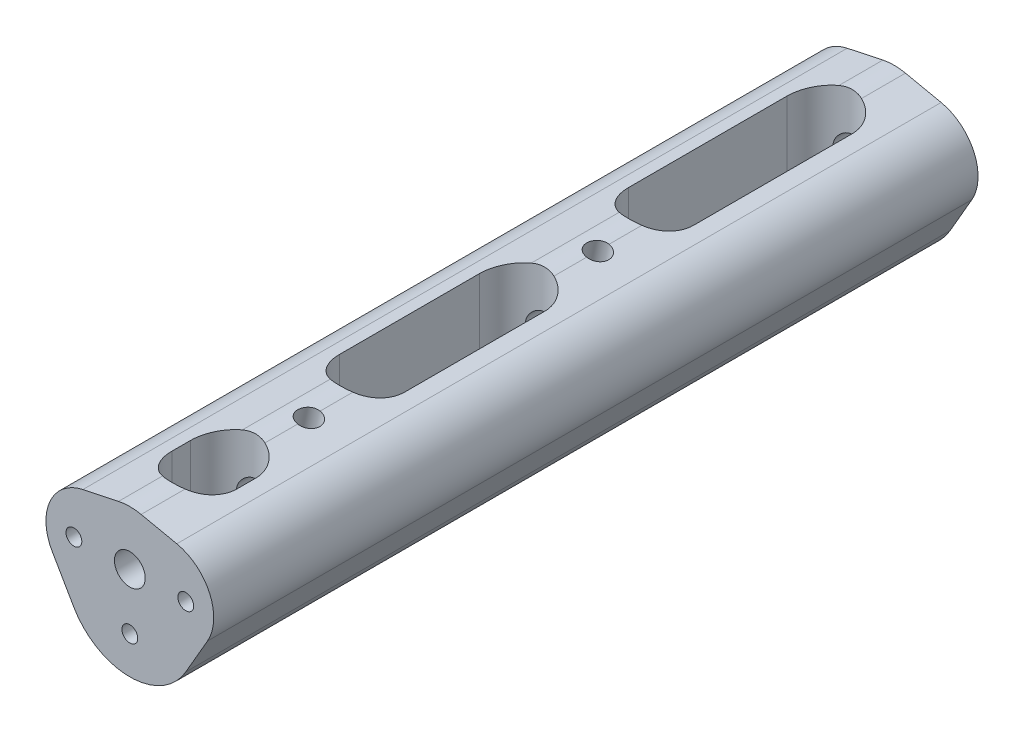
SolidWorks part; units mm, degrees
other "Pillar2"
material "Nylon 101"
ref_plane "Front" through (0, 0, 0) normal (0, 0, 1) x (1, 0, 0)
ref_plane "Top" through (0, 0, 0) normal (0, 1, 0) x (1, 0, 0)
ref_plane "Right" through (0, 0, 0) normal (1, 0, 0) x (0, 0, -1)
ref_axis "Axis" through (0, 0, -80.9) along (0, 0, 1)
sketch "BodySke" plane through (0, 0, 0) normal (0, 0, 1) x (1, 0, 0)
  line L0 (-2, 0) -> (2, 0) construction
  line L1 (-2, 2.5) -> (2, 2.5) construction
  line L2 (-2, -2.5) -> (2, -2.5) construction
  line L3 (4.1651, -1.25) -> (3, -3.2679)
  line L4 (-3, -3.2679) -> (-4.1651, -1.25)
  line L6 (2.5198, 2.4454) -> (0.6062, 2.8521)
  line L7 (-0.6062, 2.8521) -> (-2.5198, 2.4454)
  line L13 (3, 0) -> (-3, 0) construction
  arc A0 (-2, 2.5) -> (-2, -2.5) centre (-2, 0) ccw construction
  arc A1 (2, -2.5) -> (2, 2.5) centre (2, 0) ccw construction
  arc A4 (-3, -3.2679) -> (3, -3.2679) centre (0, -1.5359) ccw
  arc A5 (0.6062, 2.8521) -> (-0.6062, 2.8521) centre (0, 0) ccw
  arc A6 (4.1651, -1.25) -> (2.5198, 2.4454) centre (2, 0) ccw
  arc A7 (-4.1651, -1.25) -> (-2.5198, 2.4454) centre (-2, 0) cw
  circle A9 centre (0, 0) radius 0.825
  circle A15 centre (-3, 0) radius 0.425
  circle A16 centre (3, 0) radius 0.425
  circle A17 centre (0, -3) radius 0.425
  point P2 (0, 0)
  point P19 (0, -5)
  point P44 (0, 0)
  dimension "D3" = 1.65
  dimension "D6" = 3
  dimension "D4" = 0.85
  dimension "D5" = 12
  dimension "D1" = 4
  dimension "D2" = 5
  dimension "D7" = 5
  dimension "D8" = 6
  dimension "D10" = 6
extrude "Body" add sketch "BodySke" along normal blind 41
ref_plane "Plane" through (0, 0, 0) normal (-0.9781, 0.2079, 0) x (0, 0, 1)
sketch "HoleSke" plane through (0, 0, 0) normal (-0.9781, 0.2079, 0) x (0, 0, 1)
  line L0 (32, 3.0375) -> (32, 1.7045)
  line L1 (16.5, 3.0375) -> (16.5, 1.7045)
  line L3 (0, 1.868) -> (0, -2.0886) construction
  arc A0 (16.5, 3.0375) -> (32, 3.0375) centre (24.25, 3.0375) cw
  spline S0 degree 3 poles (10.5, 0) (15.1199, 0) (16.5, 0.036) (16.5, 1.7045) knots 0 0 0 0 1 1 1 1
  spline S1 degree 3 poles (26, 0) (30.6199, 0) (32, 0.036) (32, 1.7045) knots 0 0 0 0 1 1 1 1
  dimension "D1" = 16.5
  dimension "D2" = 10.5
  dimension "D3" = 2
sweep "Hole" cut path "HoleSke" circular profile diameter 1.2 parameters "D3"=1.2
sketch "CutSke" plane through (0, 0, 0) normal (0, 1, 0) x (1, 0, 0)
  line L0 (0, -4) -> (0, -12.5) construction
  line L1 (1.75, -4) -> (1.75, -12.5)
  line L2 (-1.75, -4) -> (-1.75, -12.5)
  line L4 (3, 0) -> (-3, 0) construction
  line L5 (0, -28) -> (0, -20.5) construction
  line L6 (-1.75, -28) -> (-1.75, -20.5)
  line L7 (1.75, -28) -> (1.75, -20.5)
  line L8 (0, -37) -> (0, -36) construction
  line L9 (-1.75, -37) -> (-1.75, -36)
  line L10 (1.75, -37) -> (1.75, -36)
  line L11 (0.6315, -16.5) -> (0.3544, -16.5) construction
  line L12 (0.6315, -32) -> (0.3544, -32) construction
  line L13 (2.5198, -41) -> (0.6062, -41) construction
  arc A0 (1.75, -4) -> (-1.75, -4) centre (0, -4) ccw
  arc A1 (-1.75, -12.5) -> (1.75, -12.5) centre (0, -12.5) ccw
  arc A2 (-1.75, -28) -> (1.75, -28) centre (0, -28) ccw
  arc A3 (1.75, -20.5) -> (-1.75, -20.5) centre (0, -20.5) ccw
  arc A4 (-1.75, -37) -> (1.75, -37) centre (0, -37) ccw
  arc A5 (1.75, -36) -> (-1.75, -36) centre (0, -36) ccw
  point P2 (0, -8.25)
  point P9 (0, -24.25)
  point P18 (0, -36.5)
  dimension "D1" = 4
  dimension "D2" = 4
  dimension "D3" = 3.5
  dimension "D4" = 4
  dimension "D5" = 4
  dimension "D6" = 4
  dimension "D7" = 4
extrude "Cut" cut sketch "CutSke" against normal through all and the other way through all
